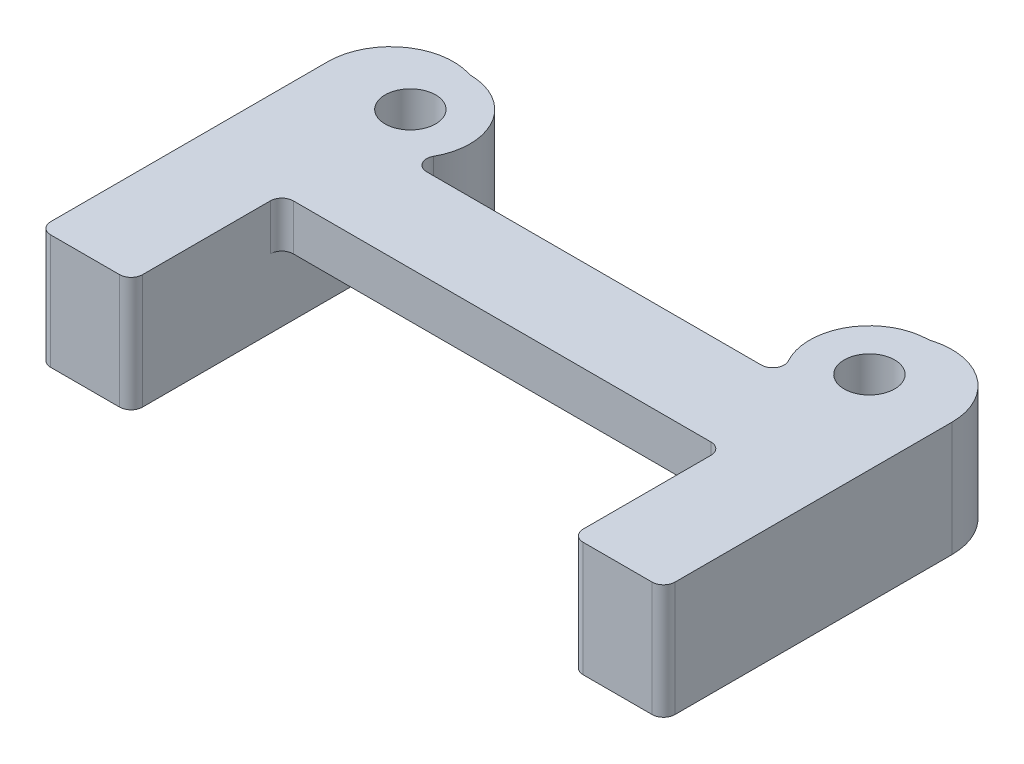
SolidWorks part; units mm, degrees
ref_plane "Front Plane" through (0, 0, 0) normal (0, 0, 1) x (1, 0, 0)
ref_plane "Top Plane" through (0, 0, 0) normal (0, 1, 0) x (1, 0, 0)
ref_plane "Right Plane" through (0, 0, 0) normal (1, 0, 0) x (0, 0, -1)
sketch "Sketch1" plane through (0, 0, 0) normal (0, 1, 0) x (1, 0, 0)
  line L0 (2.6, 0) -> (3.6, 0) construction
  line L1 (3.6, 0) -> (3.6, -12.569)
  line L2 (3.6, -12.569) -> (-0.4, -12.569)
  line L3 (-0.4, -12.569) -> (-0.4, -2.569)
  arc A0 (0, 2.6) -> (-0.4, -2.569) centre (0, 0) ccw
  circle A1 centre (0, 0) radius 1.1
  arc A2 (0, 2.6) -> (3.6, 0) centre (0.8611, 0) cw
  arc A3 (-0.4, -2.569) -> (2.6, 0) centre (0, 0) ccw construction
  arc A4 (2.6, 0) -> (0, 2.6) centre (0, 0) ccw construction
  dimension "D1" = 5.2
  dimension "D2" = 2.2
  dimension "D3" = 1
  dimension "D4" = 4
  dimension "D5" = 10
extrude "Base" add sketch "Sketch1" along normal blind 5
sketch "Sketch2" plane through (0, 5, 0) normal (0, 1, 0) x (1, 0, 0)
  line L0 (0, 0) -> (0, -2) construction
  line L1 (0, -2) -> (-10, -2)
  line L2 (-10, -2) -> (-10, -6)
  line L3 (-10, -6) -> (0, -6)
  line L4 (0, -6) -> (0, -2)
  arc M5 (0, 2.6) -> (-0.4, -2.569) centre (0, 0) ccw
  line M6 (-0.4, -2.569) -> (-0.4, -12.569)
  dimension "D1" = 2
  dimension "D2" = 4
  dimension "D3" = 10
extrude "Boss-Extrude2" add sketch "Sketch2" against normal blind 2 contours L2 L3 L1 M6 M5 region at (-5.2509, 5, 4.021)
ref_plane "Plane1" through (-10, 0, 0) normal (-1, 0, 0) x (0, 0, 1)
mirror "Mirror2" about plane through (-10, 0, 0) normal (-1, 0, 0) of bodies 102
fillet "Fillet1" radius 0.5 12 edges at (-20, 2.5, -2.6) (0, 2.5, -2.6) (-0.4, 1.5, 2.569) (-19.6, 1.5, 2.569) (-18.3387, 4, 2) (-1.6613, 4, 2) (3.6, 2.5, 12.569) (-0.4, 2.5, 12.569) (-0.4, 4, 6) (-19.6, 4, 6) (-23.6, 2.5, 12.569) (-19.6, 2.5, 12.569)
